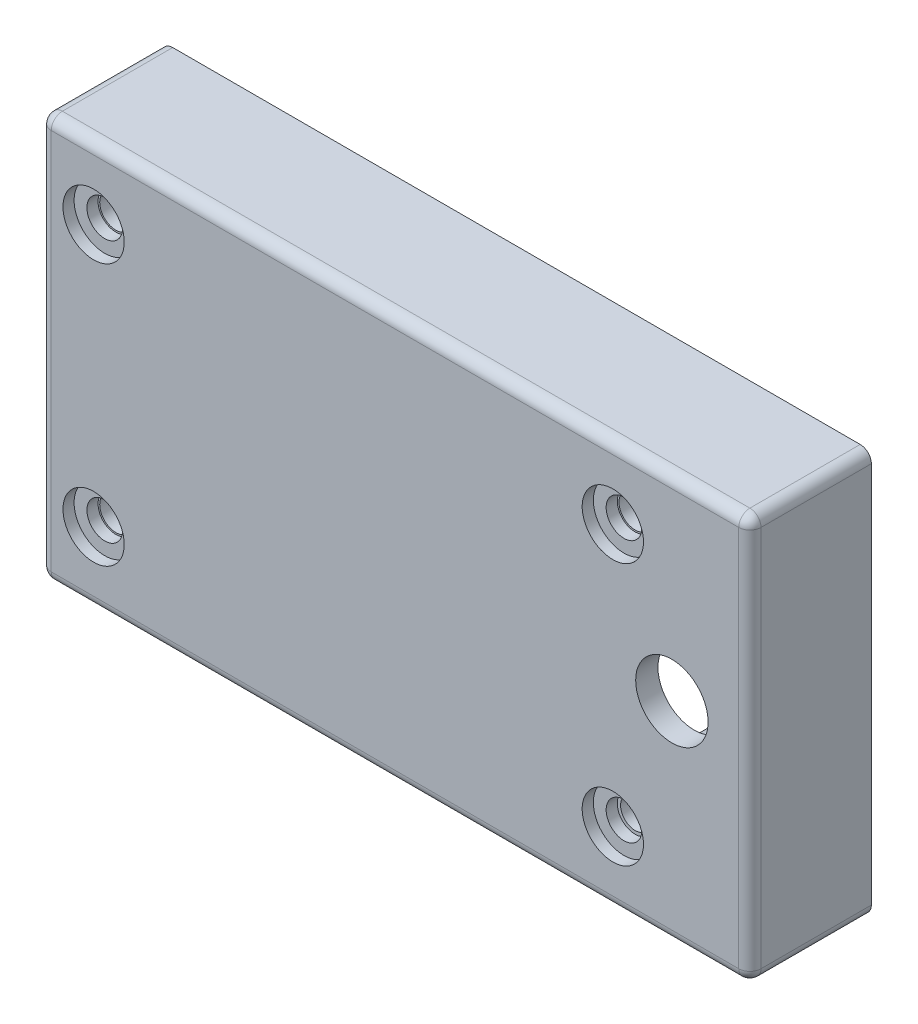
SolidWorks part; units mm, degrees
ref_plane "Alzado" through (0, 0, 0) normal (0, 0, 1) x (1, 0, 0)
ref_plane "Planta" through (0, 0, 0) normal (0, 1, 0) x (1, 0, 0)
ref_plane "Vista lateral" through (0, 0, 0) normal (1, 0, 0) x (0, 0, -1)
sketch "Croquis1" plane through (0, 0, 0) normal (0, 0, 1) x (1, 0, 0)
  line L0 (-27.2842, -16.3489) -> (32.4158, -16.3489) construction
  line L1 (-29.2842, -18.3489) -> (34.4158, -18.3489)
  line L2 (-29.2842, -18.3489) -> (-29.2842, 17.9511)
  line L3 (-29.2842, 17.9511) -> (34.4158, 17.9511)
  line L4 (34.4158, -18.3489) -> (34.4158, 17.9511)
  line L5 (32.4158, -16.3489) -> (-27.2842, -16.3489)
  line L6 (32.4158, -16.3489) -> (32.4158, 15.9511)
  line L7 (32.4158, 15.9511) -> (-27.2842, 15.9511)
  line L8 (-27.2842, -16.3489) -> (-27.2842, 15.9511)
  line L9 (32.4158, -16.3489) -> (32.4158, 15.9511) construction
sketch "Croquis2" plane through (-1.3633, 4.2361, 1) normal (0, 0, 1) x (0, 1, 0)
  circle A0 centre (-16.185, 23.1209) radius 1.45
  circle A1 centre (-16.185, 23.1209) radius 2.4
  circle A2 centre (7.315, 23.1209) radius 1.45
  circle A3 centre (7.315, 23.1209) radius 2.4
  circle A4 centre (7.315, -23.4791) radius 1.45
  circle A5 centre (7.315, -23.4791) radius 2.2627
  circle A6 centre (-16.185, -23.4791) radius 1.3049
  circle A7 centre (-16.185, -23.4791) radius 2.4
extrude "Saliente-Extruir2" add sketch "Croquis2" against normal up to surface (12.3 mm away) separate body
sketch "Croquis4" plane through (-1.3633, 4.2361, 1) normal (0, 0, 1) x (0, 1, 0)
  line L0 (-20.585, -33.7791) -> (11.715, -33.7791) construction
  line L1 (13.715, 27.9209) -> (-22.585, 27.9209)
  line L2 (13.715, 27.9209) -> (13.715, -35.7791)
  line L3 (13.715, -35.7791) -> (-22.585, -35.7791)
  line L4 (-22.585, 27.9209) -> (-22.585, -35.7791)
  line L5 (-20.585, -33.7791) -> (11.715, -33.7791)
  line L6 (-20.585, -33.7791) -> (-20.585, 25.9209)
  line L7 (-20.585, 25.9209) -> (11.715, 25.9209)
  line L8 (11.715, -33.7791) -> (11.715, 25.9209)
  line L9 (-20.585, 25.9209) -> (-20.585, -33.7791) construction
extrude "Saliente-Extruir4" add sketch "Croquis4" against normal up to surface (8.9 mm away) separate body
sketch "Croquis5" plane through (-1.3633, 4.2361, 1) normal (0, 0, 1) x (0, 1, 0)
  line L1 (-22.585, 27.9209) -> (13.715, 27.9209)
  line L2 (-22.585, 27.9209) -> (-22.585, -35.7791)
  line L3 (-22.585, -35.7791) -> (13.715, -35.7791)
  line L4 (13.715, 27.9209) -> (13.715, -35.7791)
extrude "Saliente-Extruir5" add sketch "Croquis5" along normal blind 2
fillet "Redondeo1" radius 1 8 edges at (-29.2842, -0.1989, 3) (2.5658, 17.9511, 3) (34.4158, -0.1989, 3) (2.5658, -18.3489, 3) (34.4158, -18.3489, -2.45) (34.4158, 17.9511, -2.45) (-29.2842, 17.9511, -2.45) (-29.2842, -18.3489, -2.45)
sketch "Croquis6" plane through (-29.2842, 0, 0) normal (-1, 0, 0) x (0, 0, 1)
  line L0 (-7.9, -17.3489) -> (-7.9, 16.9511) construction
  line L1 (-7.9, -5.7361) -> (-6.9475, -5.7361)
  line L2 (-7.9, -5.7361) -> (-7.9, 5.2936)
  line L3 (-7.9, 5.2936) -> (-6.9475, 5.2936)
  line L4 (-6.9475, -5.7361) -> (-6.9475, 5.2936)
  line L5 (-12.7896, -5.7361) -> (-7.9, -5.7361) construction
extrude "Cortar-Extruir1" cut sketch "Croquis6" against normal blind 1
fillet "Redondeo2" radius 1 3 edges at (-29.2842, -5.7361, -7.4238) (-29.2842, 5.2936, -7.4238) (-29.2842, -0.2212, -6.9475)
sketch "Croquis7" plane through (0, 0, -11.3) normal (0, 0, -1) x (-1, 0, 0)
  circle A0 centre (24.4842, 11.5511) radius 1.45
  circle A1 centre (24.4842, -11.9489) radius 1.45
  circle A2 centre (-22.1158, -11.9489) radius 1.3049
  circle A3 centre (-22.1158, 11.5511) radius 1.45
extrude "Cortar-Extruir2" cut sketch "Croquis7" against normal through all
sketch "Croquis8" plane through (0, 0, 3) normal (0, 0, 1) x (1, 0, 0)
  circle A0 centre (-24.4842, -11.9489) radius 2.75
  circle A1 centre (-24.4842, 11.5511) radius 2.75
  circle A2 centre (22.1158, -11.9489) radius 2.75
  circle A3 centre (22.1158, 11.5511) radius 2.75
  dimension "D1" = 5.5
  dimension "D2" = 5.5
  dimension "D3" = 5.5
  dimension "D4" = 5.5
extrude "Cortar-Extruir3" cut sketch "Croquis8" against normal blind 1
sketch "Croquis9" plane through (0, 0, 1) normal (0, 0, -1) x (-1, 0, 0)
  line L0 (-32.4158, -16.3489) -> (-32.4158, 15.9511) construction
  line L9 (-32.4158, 15.9511) -> (27.2842, 15.9511) construction
  circle A0 centre (-27.4158, 0.4511) radius 3.2502
  dimension "D1" = 6.5004
  dimension "D2" = 5
  dimension "D3" = 15.5
extrude "Cortar-Extruir4" cut sketch "Croquis9" against normal through all
sketch "Croquis10" plane through (0, 0, 1) normal (0, 0, -1) x (-1, 0, 0)
  line L17 (-14.0598, 10.3107) -> (14.5295, 10.3107)
  line L18 (-14.0598, 10.3107) -> (-14.0598, -10.3255)
  line L19 (-14.0598, -10.3255) -> (14.5295, -10.3255)
  line L20 (14.5295, 10.3107) -> (14.5295, -10.3255)
  line L21 (-15.0598, 11.3107) -> (15.5295, 11.3107)
  line L22 (-15.0598, 11.3107) -> (-15.0598, -11.3255)
  line L23 (-15.0598, -11.3255) -> (15.5295, -11.3255)
  line L24 (15.5295, 11.3107) -> (15.5295, -11.3255)
  dimension "D1" = 1
  dimension "D2" = 1
  dimension "D3" = 1
  dimension "D4" = 1
extrude "Saliente-Extruir6" add sketch "Croquis10" along normal blind 2.5
sketch "Croquis11" plane through (0, 0, 1) normal (0, 0, -1) x (-1, 0, 0)
  circle A0 centre (-22.1158, 11.5511) radius 1.6
  circle A1 centre (24.4842, 11.5511) radius 1.6
  circle A2 centre (24.4842, -11.9489) radius 1.6
  circle A3 centre (-22.1158, -11.9489) radius 1.6
  dimension "D1" = 3.2
  dimension "D2" = 3.2
  dimension "D3" = 3.2
  dimension "D4" = 3.2
extrude "Cortar-Extruir5" cut sketch "Croquis11" against normal through all
